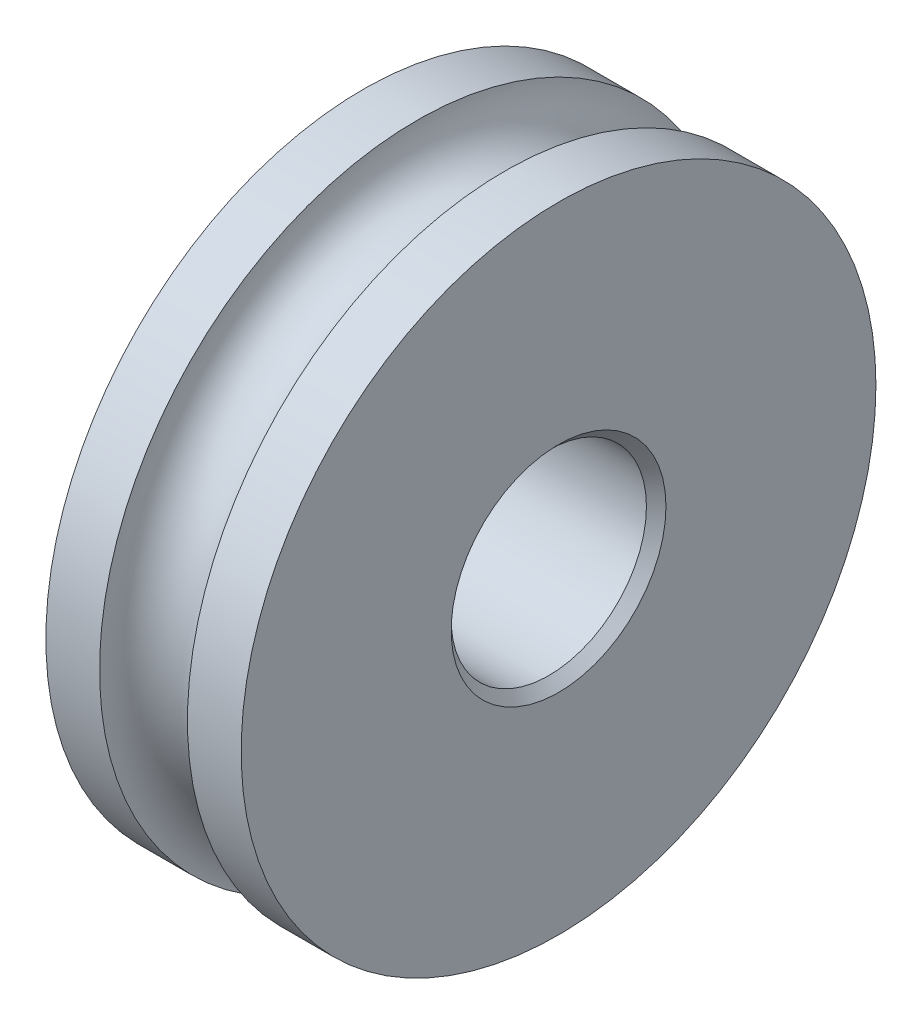
SolidWorks part; units mm, degrees
ref_plane "Спереди" through (0, 0, 0) normal (0, 0, 1) x (1, 0, 0)
ref_plane "Сверху" through (0, 0, 0) normal (0, 1, 0) x (1, 0, 0)
ref_plane "Справа" through (0, 0, 0) normal (1, 0, 0) x (0, 0, -1)
sketch "Эскиз3" plane through (0, 0, 0) normal (0, 0, 1) x (1, 0, 0)
  line L0 (7.1882, 0) -> (-5.8346, 0) construction
  line L1 (0, 2) -> (4, 2)
  line L2 (0, 2) -> (0, 6.5)
  line L3 (0, 6.5) -> (1.1, 6.5)
  line L4 (4, 2) -> (4, 6.5)
  line L5 (2.9, 6.5) -> (4, 6.5)
  arc A0 (1.1, 6.5) -> (2.9, 6.5) centre (2, 6.5) ccw
  dimension "D4" = 0.9
  dimension "D1" = 4
  dimension "D2" = 6.5
  dimension "D3" = 2
  dimension "D5" = 2
revolve "Повернуть1" add sketch "Эскиз3" angle 360 about L0
chamfer "Фаска1" distance 0.2 angle 45 2 edges at (0, 0, -2) (4, 0, -2)
